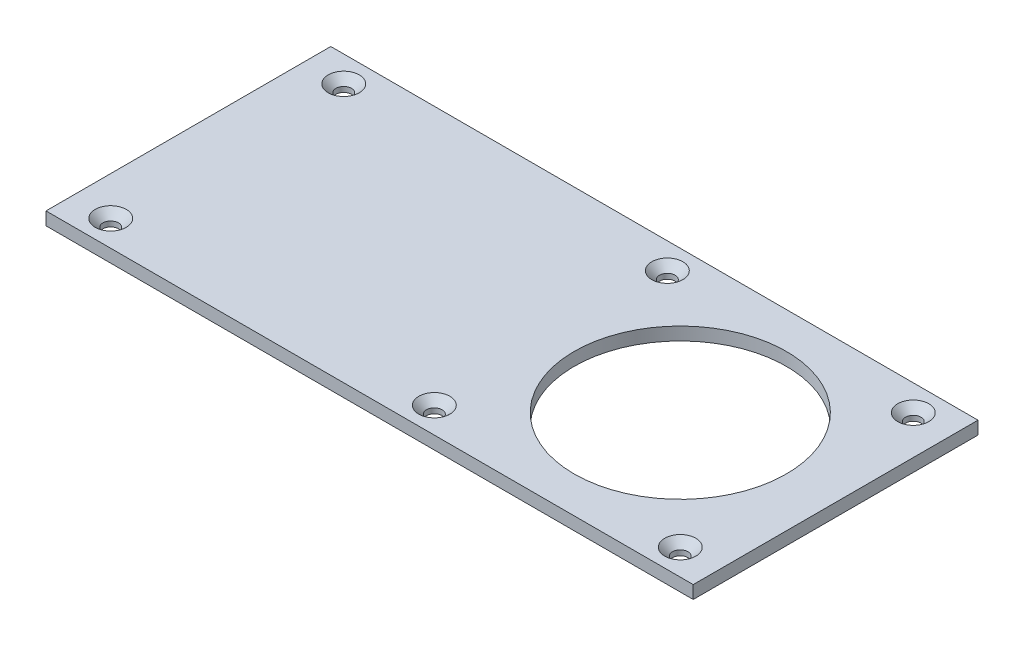
SolidWorks part; units mm, degrees
material "Сталь 3 ГОСТ 535-88"
ref_plane "Спереди" through (0, 0, 0) normal (0, 0, 1) x (1, 0, 0)
ref_plane "Сверху" through (0, 0, 0) normal (0, 1, 0) x (1, 0, 0)
ref_plane "Справа" through (0, 0, 0) normal (1, 0, 0) x (0, 0, -1)
sketch "Эскиз1" plane through (0, 0, 0) normal (0, 1, 0) x (1, 0, 0)
  line L1 (-125, -55) -> (125, -55)
  line L2 (-125, -55) -> (-125, 55)
  line L3 (-125, 55) -> (125, 55)
  line L4 (125, -55) -> (125, 55)
  line L5 (0, 55) -> (0, -55) construction
  line L6 (-125, 0) -> (125, 0) construction
  circle A0 centre (65, 0) radius 41
  point P0 (0, 0)
  dimension "D3" = 82
  dimension "D1" = 250
  dimension "D2" = 110
  dimension "D4" = 60
extrude "Бобышка-Вытянуть1" add sketch "Эскиз1" along normal blind 5
sketch "Эскиз2" plane through (0, 5, 0) normal (0, 1, 0) x (1, 0, 0)
  circle A9 centre (110, -45) radius 3 construction
  circle A12 centre (-110, -45) radius 3 construction
  circle A13 centre (15, -45) radius 3 construction
  circle A15 centre (110, -45) radius 3
  circle A18 centre (-110, -45) radius 3
  circle A19 centre (15, -45) radius 3
  circle A20 centre (-110, 45) radius 3 construction
  circle A21 centre (15, 45) radius 3 construction
  circle A22 centre (110, 45) radius 3 construction
  circle A23 centre (-110, 45) radius 3
  circle A24 centre (15, 45) radius 3
  circle A25 centre (110, 45) radius 3
extrude "Вырез-Вытянуть1" cut sketch "Эскиз2" against normal through all
chamfer "Фаска1" distance 3 angle 45 6 edges at (-110, 5, 48) (110, 5, -42) (15, 5, -42) (15, 5, 48) (110, 5, 48) (-110, 5, -42)
